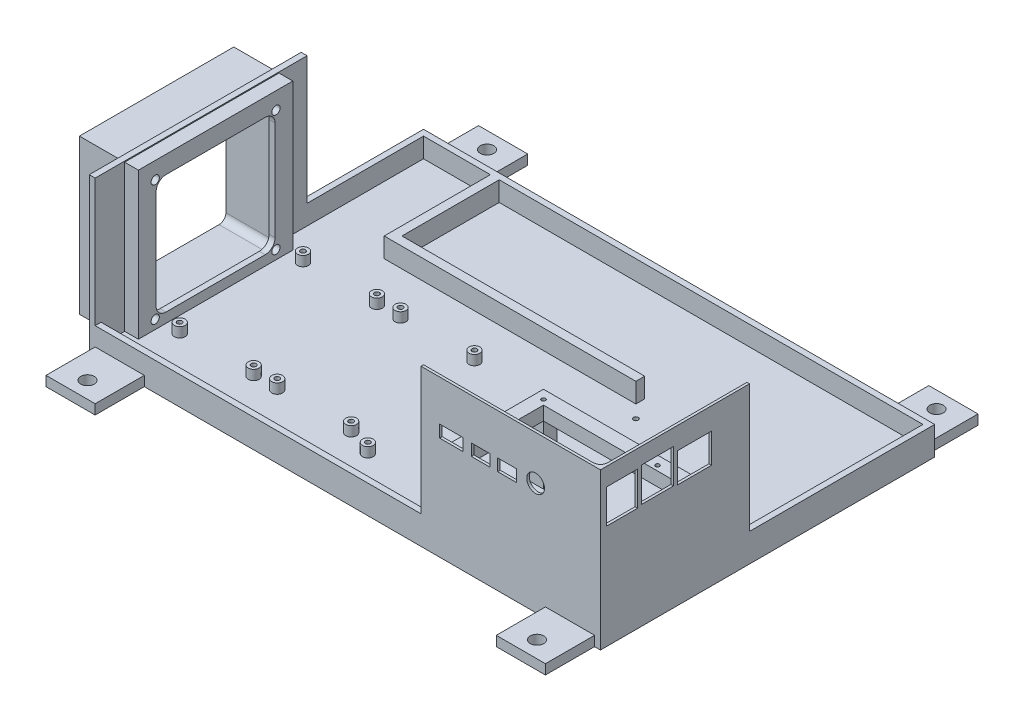
SolidWorks part; units mm, degrees
ref_plane "Front Plane" through (0, 0, 0) normal (0, 0, 1) x (1, 0, 0)
ref_plane "Top Plane" through (0, 0, 0) normal (0, 1, 0) x (1, 0, 0)
ref_plane "Right Plane" through (0, 0, 0) normal (1, 0, 0) x (0, 0, -1)
sketch "Sketch1" plane through (0, 0, 0) normal (0, 1, 0) x (1, 0, 0)
  line L1 (-130, -85) -> (130, -85)
  line L2 (-130, -85) -> (-130, 85)
  line L3 (-130, 85) -> (130, 85)
  line L4 (130, -85) -> (130, 85)
  line L5 (-130, -85) -> (130, 85) construction
  line L6 (-130, 85) -> (130, -85) construction
  point P0 (0, 0)
  dimension "D1" = 170
  dimension "D2" = 260
extrude "Floor" add sketch "Sketch1" along normal blind 4.3805
sketch "Sketch2" plane through (0, 4.3805, 0) normal (0, 1, 0) x (1, 0, 0)
  line L0 (127, -82) -> (127, 82)
  line L1 (127, 82) -> (-127, 82)
  line L2 (-127, 82) -> (-127, -82)
  line L3 (-127, -82) -> (127, -82)
  line L4 (130, -85) -> (130, 85)
  line L5 (130, 85) -> (-130, 85)
  line L6 (-130, 85) -> (-130, -85)
  line L7 (-130, -85) -> (130, -85)
  line L8 (130, -85) -> (130, 85)
  line L9 (130, 85) -> (-130, 85)
  line L10 (-130, 85) -> (-130, -85)
  line L11 (-130, -85) -> (130, -85)
  dimension "D1" = 0
  dimension "D2" = 3
extrude "Wall" add sketch "Sketch2" along normal blind 10
sketch "Sketch4" plane through (0, 4.3805, 0) normal (0, 1, 0) x (1, 0, 0)
  line L0 (120, -33) -> (49, -33)
  line L1 (127, -82) -> (42, -82)
  line L2 (127, -82) -> (127, -26)
  line L3 (127, -26) -> (42, -26)
  line L4 (42, -82) -> (42, -26)
  line L5 (49, -75) -> (49, -33)
  line L6 (120, -75) -> (49, -75)
  line L7 (120, -75) -> (120, -33)
  dimension "D1" = 85
  dimension "D2" = 56
  dimension "D3" = 7
extrude "Rpi stand" add sketch "Sketch4" along normal blind 7 from offset 30
sketch "Sketch7" plane through (0, 14.3805, 0) normal (0, 1, 0) x (1, 0, 0)
  line L0 (-127, 82) -> (-127, -82) construction
  line L1 (-130, -85) -> (-127, -85)
  line L2 (-130, -85) -> (-130, 22.7839)
  line L3 (-130, 22.7839) -> (-127, 22.7839)
  line L4 (-127, -85) -> (-127, 22.7839)
  line L5 (-127, -82) -> (127, -82) construction
  line L6 (130, -85) -> (38.7223, -85)
  line L7 (130, -85) -> (130, -52.9248)
  line L8 (127, -82) -> (38.7223, -82)
  line L9 (38.7223, -85) -> (38.7223, -82)
  line L10 (127, -82) -> (127, 82) construction
  line L12 (130, -52.9248) -> (130, -9.2525)
  line L13 (130, -9.2525) -> (127, -9.2525)
  line L14 (127, -82) -> (127, -9.2525)
  line L15 (-127, -82) -> (127, -82) construction
  line L16 (130, -85) -> (130, 85) construction
extrude "Temp support" add sketch "Sketch7" along normal blind 65
sketch "Sketch3" plane through (0, 0, 0) normal (0, 1, 0) x (1, 0, 0)
  line L0 (-114.3, 101.6) -> (114.3, 101.6) construction
  line L1 (-127, 85) -> (-102, 85)
  line L2 (-127, 85) -> (-127, 110)
  line L3 (-127, 110) -> (-102, 110)
  line L4 (-102, 85) -> (-102, 110)
  line L5 (127, 85) -> (102, 85)
  line L6 (127, 85) -> (127, 110)
  line L7 (127, 110) -> (102, 110)
  line L8 (102, 85) -> (102, 110)
  line L9 (-127, -85) -> (-102, -85)
  line L10 (-127, -85) -> (-127, -110)
  line L11 (-127, -110) -> (-102, -110)
  line L12 (-102, -85) -> (-102, -110)
  line L13 (127, -85) -> (102, -85)
  line L14 (127, -85) -> (127, -110)
  line L15 (127, -110) -> (102, -110)
  line L16 (102, -85) -> (102, -110)
  line L17 (114.3, 101.6) -> (114.3, -101.6) construction
  line L18 (114.3, -101.6) -> (-114.3, -101.6) construction
  line L19 (-114.3, -101.6) -> (-114.3, 101.6) construction
  line L20 (-130, 37.8738) -> (130, 37.8738) construction
  line L21 (130, 85) -> (-130, 85) construction
  line L22 (130, -9.2525) -> (130, 85) construction
  line L23 (0, 101.6) -> (0, -101.6) construction
  line L24 (-130, 22.7839) -> (-130, -85) construction
  line L29 (38.7223, -85) -> (130, -85) construction
  line L30 (-127, -85) -> (38.7223, -85) construction
  circle A0 centre (-114.3, 101.6) radius 3.429
  circle A1 centre (114.3, 101.6) radius 3.429
  circle A2 centre (114.3, -101.6) radius 3.429
  circle A3 centre (-114.3, -101.6) radius 3.429
  point P28 (-114.5, -85)
  point P29 (-102, -97.5)
  point P30 (114.5, -85)
  point P31 (-102, 97.5)
  dimension "D5" = 6.858
  dimension "D1" = 25
  dimension "D2" = 25
  dimension "D3" = 25
  dimension "D6" = 203.2
  dimension "D7" = 228.6
  dimension "D8" = 3
  dimension "D9" = 3
  dimension "D4" = 25
extrude "Brackets" add sketch "Sketch3" along normal blind 5
sketch "Sketch5" plane through (-130, 0, 0) normal (-1, 0, 0) x (0, 0, 1)
  line L0 (-8.5, 78.8805) -> (70, 78.8805)
  line L1 (-1, 4.3805) -> (62.5, 4.3805)
  line L2 (-4.5, 7.8805) -> (-4.5, 71.3805)
  line L3 (-1, 74.8805) -> (62.5, 74.8805)
  line L4 (66, 7.8805) -> (66, 71.3805)
  line L5 (70, 0.3805) -> (70, 78.8805)
  line L6 (-8.5, 0.3805) -> (70, 0.3805)
  line L7 (-8.5, 0.3805) -> (-8.5, 78.8805)
  line L8 (-4.5, 4.3805) -> (66, 4.3805) construction
  line L9 (110, 5) -> (110, 0) construction
  line L10 (-4.5, 4.3805) -> (-4.5, 74.8805) construction
  line L11 (-82, 4.3805) -> (82, 4.3805) construction
  line L12 (66, 4.3805) -> (66, 74.8805) construction
  line L13 (-4.5, 74.8805) -> (66, 74.8805) construction
  arc A0 (-1, 4.3805) -> (-4.5, 7.8805) centre (-1, 7.8805) cw
  arc A1 (62.5, 4.3805) -> (66, 7.8805) centre (62.5, 7.8805) ccw
  arc A2 (62.5, 74.8805) -> (66, 71.3805) centre (62.5, 71.3805) cw
  arc A3 (-4.5, 71.3805) -> (-1, 74.8805) centre (-1, 71.3805) cw
  dimension "D4" = 3.5
  dimension "D1" = 70.5
  dimension "D2" = 70.5
  dimension "D5" = 40
  dimension "D3" = 4
extrude "Fan Holder" add sketch "Sketch5" along normal blind 20 and the other way blind 10
sketch "Sketch8" plane through (-130, 0, 0) normal (-1, 0, 0) x (0, 0, 1)
  line L4 (-4.5, 71.3805) -> (-4.5, 7.8805)
  line L5 (-1, 4.3805) -> (62.5, 4.3805)
  line L6 (66, 7.8805) -> (66, 71.3805)
  line L7 (62.5, 74.8805) -> (-1, 74.8805)
  line L8 (-4.5, 71.3805) -> (-4.5, 7.8805)
  line L9 (-1, 4.3805) -> (62.5, 4.3805)
  line L10 (66, 7.8805) -> (66, 71.3805)
  line L20 (62.5, 74.8805) -> (-1, 74.8805)
  arc A2 (-4.5, 7.8805) -> (-1, 4.3805) centre (-1, 7.8805) ccw
  arc A3 (-4.5, 7.8805) -> (-1, 4.3805) centre (-1, 7.8805) ccw
  arc A4 (62.5, 4.3805) -> (66, 7.8805) centre (62.5, 7.8805) ccw
  arc A5 (62.5, 4.3805) -> (66, 7.8805) centre (62.5, 7.8805) ccw
  arc A8 (66, 71.3805) -> (62.5, 74.8805) centre (62.5, 71.3805) ccw
  arc A12 (66, 71.3805) -> (62.5, 74.8805) centre (62.5, 71.3805) ccw
  arc A14 (-1, 74.8805) -> (-4.5, 71.3805) centre (-1, 71.3805) ccw
  arc A15 (-1, 74.8805) -> (-4.5, 71.3805) centre (-1, 71.3805) ccw
  dimension "D1" = 0
extrude "Fan hole" cut sketch "Sketch8" against normal up to next (3 mm away)
sketch "Sketch11" plane through (-120, 0, 0) normal (-1, 0, 0) x (0, 0, 1)
  line L0 (-8.5, 39.6305) -> (70, 39.6305) construction
  line L1 (30.75, 78.8805) -> (30.75, 0.3805) construction
  line L3 (0.05, 8.9305) -> (61.45, 8.9305) construction
  line L4 (-8.5, 78.8805) -> (-8.5, 0.3805)
  line L5 (-8.5, 0.3805) -> (70, 0.3805)
  line L6 (70, 0.3805) -> (70, 78.8805)
  line L7 (70, 78.8805) -> (-8.5, 78.8805)
  line L8 (-8.5, 78.8805) -> (-8.5, 0.3805)
  line L9 (-8.5, 0.3805) -> (70, 0.3805)
  line L10 (70, 0.3805) -> (70, 78.8805)
  line L11 (70, 78.8805) -> (-8.5, 78.8805)
  line L12 (0.05, 8.9305) -> (0.05, 70.3305) construction
  line L13 (0.05, 70.3305) -> (61.45, 70.3305) construction
  line L14 (61.45, 8.9305) -> (61.45, 70.3305) construction
  line L15 (0.05, 8.9305) -> (61.45, 70.3305) construction
  line L16 (0.5, 69.8805) -> (0.5, 9.3805)
  line L17 (0.5, 9.3805) -> (61, 9.3805)
  line L18 (61, 9.3805) -> (61, 69.8805)
  line L19 (61, 69.8805) -> (0.5, 69.8805)
  line L20 (0.5, 64.8805) -> (0.5, 14.3805)
  line L21 (5.5, 9.3805) -> (56, 9.3805)
  line L22 (61, 14.3805) -> (61, 64.8805)
  line L23 (56, 69.8805) -> (5.5, 69.8805)
  line L24 (0.05, 70.3305) -> (61.45, 8.9305) construction
  arc A0 (0.5, 14.3805) -> (5.5, 9.3805) centre (5.5, 14.3805) ccw
  arc A1 (56, 9.3805) -> (61, 14.3805) centre (56, 14.3805) ccw
  arc A2 (61, 64.8805) -> (56, 69.8805) centre (56, 64.8805) ccw
  arc A3 (0.5, 64.8805) -> (5.5, 69.8805) centre (5.5, 64.8805) cw
  circle A4 centre (0.05, 70.3305) radius 2.1
  circle A5 centre (61.45, 70.3305) radius 2.1
  circle A6 centre (61.45, 8.9305) radius 2.1
  circle A7 centre (0.05, 8.9305) radius 2.1
  point P24 (30.75, 39.6305)
  point P34 (30.75, 39.6305)
  dimension "D3" = 5
  dimension "D6" = 4.2
  dimension "D4" = 61.4
  dimension "D5" = 61.4
  dimension "D1" = 0
  dimension "D2" = 9
extrude "Boss-Extrude9" add sketch "Sketch11" along normal blind 3
sketch "Sketch12" plane through (0, 34.3805, 0) normal (0, -1, 0) x (1, 0, 0)
  line L1 (42, 26) -> (49, 26)
  line L2 (42, 26) -> (42, 33)
  line L3 (42, 33) -> (49, 33)
  line L4 (49, 26) -> (49, 33)
  dimension "D1" = 7
  dimension "D2" = 7
extrude "Boss-Extrude10" add sketch "Sketch12" along normal up to next
sketch "Sketch13" plane through (0, 4.3805, 0) normal (0, 1, 0) x (1, 0, 0)
  line L0 (-127, -82) -> (127, -82) construction
  line L1 (-127, -85) -> (-127, 22.7839) construction
  line L2 (-112, -57) -> (-112, 5.7) construction
  line L3 (-112, 5.7) -> (-74.4, 5.7) construction
  line L4 (-112, -57) -> (-74.4, -57) construction
  line L5 (-74.4, 5.7) -> (-74.4, -57) construction
  line L6 (-74.4, 5.7) -> (-62.4, 5.7) construction
  line L7 (-62.4, 5.7) -> (-62.4, -57) construction
  line L8 (-62.4, -57) -> (-24.8, -57) construction
  line L9 (-24.8, -57) -> (-24.8, 5.7) construction
  line L10 (-24.8, 5.7) -> (-62.4, 5.7) construction
  line L11 (-74.4, -57) -> (-62.4, -57) construction
  line L12 (-24.8, -57) -> (62.83, -57) construction
  line L13 (62.83, -57) -> (62.83, -25.4) construction
  line L14 (62.83, -25.4) -> (105, -25.4) construction
  line L15 (105, -25.4) -> (105, -57) construction
  line L16 (105, -57) -> (62.83, -57) construction
  line L17 (118, 82) -> (118, 21.5) construction
  line L18 (-21.3, -57.85) -> (-21.3, 6.55) construction
  line L19 (127, 82) -> (-127, 82) construction
  line L20 (127, -9.2525) -> (127, 82) construction
  line L21 (118, 21.5) -> (120.7, 21.5) construction
  line L22 (118, 21.5) -> (41.5, 21.5) construction
  line L23 (-11.3, -62) -> (25.69, -62) construction
  line L24 (-11.3, -62) -> (-11.3, -21.4) construction
  line L25 (-11.3, -21.4) -> (25.69, -21.4) construction
  line L26 (25.69, -62) -> (25.69, -21.4) construction
  line L27 (-11.3, -62) -> (25.69, -21.4) construction
  line L28 (-11.3, -21.4) -> (25.69, -62) construction
  line L29 (130, -9.2525) -> (130, 85) construction
  line L30 (-127, -82) -> (38.7223, -82) construction
  circle A0 centre (-112, -57) radius 1.25
  circle A1 centre (-112, 5.7) radius 1.25
  circle A2 centre (-74.4, 5.7) radius 1.25
  circle A3 centre (-74.4, -57) radius 1.25
  circle A4 centre (-62.4, 5.7) radius 1.25
  circle A5 centre (-62.4, -57) radius 1.25
  circle A6 centre (-24.8, -57) radius 1.25
  circle A7 centre (-24.8, 5.7) radius 1.25
  circle A12 centre (120.7, 21.5) radius 1.25
  circle A13 centre (41.5, 21.5) radius 1.25
  circle A14 centre (-112, 5.7) radius 2.75
  circle A15 centre (-112, -57) radius 2.75
  circle A16 centre (-74.4, 5.7) radius 2.75
  circle A17 centre (-62.4, 5.7) radius 2.75
  circle A18 centre (-74.4, -57) radius 2.75
  circle A19 centre (-62.4, -57) radius 2.75
  circle A20 centre (-24.8, -57) radius 2.75
  circle A21 centre (-24.8, 5.7) radius 2.75
  circle A22 centre (62.83, -57) radius 2.5
  circle A23 centre (62.83, -25.4) radius 2.5
  circle A24 centre (105, -25.4) radius 2.5
  circle A25 centre (105, -57) radius 2.5
  circle A26 centre (-11.3, -62) radius 1.25
  circle A28 centre (-11.3, -62) radius 2.75
  circle A30 centre (-74.4, 5.7) radius 1.65 construction
  circle A31 centre (104.2333, -41.2) radius 1.5 construction
  circle A32 centre (104.2333, -41.2) radius 1.5 construction
  circle A33 centre (63.5933, -41.2) radius 1.5 construction
  circle A34 centre (63.5933, -41.2) radius 1.5 construction
  circle A35 centre (104.2333, -41.2) radius 3
  circle A36 centre (63.5933, -41.2) radius 3
  circle A37 centre (-11.3, -21.4) radius 1.25
  circle A38 centre (25.69, -21.4) radius 1.25
  circle A39 centre (25.69, -62) radius 1.25
  circle A40 centre (-11.3, -21.4) radius 2.75
  circle A41 centre (25.69, -21.4) radius 2.75
  circle A42 centre (25.69, -62) radius 2.75
  circle A43 centre (25.69, -21.4) radius 1.5 construction
  circle A44 centre (25.69, -21.4) radius 1.5 construction
  point P6 (-127, -31.108)
  point P8 (7.195, -41.7)
  dimension "D1" = 25
  dimension "D2" = 15
  dimension "D3" = 2.5
  dimension "D6" = 1.5
  dimension "D7" = 2.5
  dimension "D8" = 10
  dimension "D11" = 20
  dimension "D25" = 2.5
  dimension "D27" = 2.5
  dimension "D4" = 5
  dimension "D5" = 25
  dimension "D9" = 12
  dimension "D10" = 1.5
  dimension "D17" = 31.6
  dimension "D19" = 42.17
  dimension "D22" = 60.5
  dimension "D23" = 9
  dimension "D24" = 2.7
  dimension "D26" = 76.5
  dimension "D28" = 1.5
extrude "Built in Standoffs" add sketch "Sketch13" along normal blind 5 contours A1 | A16 A2 | A2 | A17 A4 | A4 | A14 A1 | A21 A7 | A7 | A15 A0 | A0 | A18 A3 | A3 | A19 A5 | A5 | A20 A6 | A6 | A22 | A23 | A24 A32 | A32 | A25 | A36 | A35 | A28 A26 | A26 | A40 A37 | A37 | A41 A38 | A38 | A42 A39 | A39 region at (-112, 4.3805, 57) region at (-112, 4.3805, -5.7) region at (-74.4, 4.3805, -5.7) region at (-74.4, 4.3805, 57) region at (-62.4, 4.3805, -5.7) region at (-62.4, 4.3805, 57) region at (-24.8, 4.3805, 57) region at (-24.8, 4.3805, -5.7) region at (-114.6722, 4.3805, -5.7) region at (-114.6722, 4.3805, 57) region at (-77.0722, 4.3805, -5.7) region at (-65.0722, 4.3805, -5.7) region at (-77.0722, 4.3805, 57) region at (-65.0722, 4.3805, 57) region at (-27.4722, 4.3805, 57) region at (-27.4722, 4.3805, -5.7) region at (62.83, 4.3805, 57) region at (62.83, 4.3805, 25.4) region at (105, 4.3805, 25.4) region at (105, 4.3805, 57) region at (-11.3, 4.3805, 62) region at (-13.9722, 4.3805, 62) region at (104.2333, 4.3805, 41.2) region at (63.5933, 4.3805, 41.2) region at (-11.3, 4.3805, 21.4) region at (25.69, 4.3805, 21.4) region at (25.69, 4.3805, 62) region at (-13.9722, 4.3805, 21.4) region at (23.0178, 4.3805, 21.4) region at (23.0178, 4.3805, 62)
sketch "Sketch19" plane through (0, 9.3805, 0) normal (0, 1, 0) x (1, 0, 0)
  circle A0 centre (104.2333, -41.2) radius 1.25
  circle A1 centre (63.5933, -41.2) radius 1.25
  dimension "D1" = 2.5
  dimension "D2" = 2.5
extrude "Bread board holes" cut sketch "Sketch19" against normal blind 7
sketch "Sketch14" plane through (0, 4.3805, 0) normal (0, 1, 0) x (1, 0, 0)
  line L0 (127, 82) -> (-88, 82)
  line L1 (127, 82) -> (-127, 82) construction
  line L2 (-88, 82) -> (-88, 32)
  line L3 (-88, 32) -> (127, 32)
  line L4 (127, -82) -> (127, 82) construction
  line L5 (127, 32) -> (127, 82)
  dimension "D1" = 215
  dimension "D2" = 50
extrude "Screw Holes" cut sketch "Sketch13<4>" against normal blind 7 from surface contours A37 | A38 | A26 | A39 | A1 | A0 | A3 | A5 | A2 | A4 | A7 | A6 | A32 region at (-11.3, 4.3805, 62) region at (-11.3, 4.3805, 21.4) region at (25.69, 4.3805, 21.4) region at (25.69, 4.3805, 62) starting at face at (-112, 9.3805, -2.95)
sketch "Sketch13<4>" plane through (0, 4.3805, 0) normal (0, 1, 0) x (1, 0, 0) same geometry as "Sketch13"
extrude "Driver Screw Holes" cut sketch "Sketch13<5>" against normal blind 3 contours A13 | A12
sketch "Sketch13<5>" plane through (0, 4.3805, 0) normal (0, 1, 0) x (1, 0, 0) same geometry as "Sketch13"
sketch "Sketch16" plane through (0, 4.3805, 0) normal (0, 1, 0) x (1, 0, 0)
  line L0 (-93, 82) -> (-93, 28)
  line L1 (-93, 28) -> (35, 28)
  line L2 (-88.5, 82) -> (-88.5, 32.5)
  line L3 (-88.5, 32.5) -> (35, 32.5)
  line L10 (-88, 82) -> (-88, 33) construction
  line L11 (-88, 33) -> (29.1074, 33) construction
  line L14 (-93, 28) -> (127, 28) construction
  line L16 (-88, 33) -> (127, 33) construction
  line L17 (-88.5, 82) -> (-93, 82)
  line L20 (35, 28) -> (35, 32.5)
  line L21 (-88.5, 32.5) -> (29.1074, 32.5) construction
  line L25 (-88, 33) -> (127, 33)
  line L26 (127, 33) -> (127, 82)
  line L27 (127, 82) -> (-88, 82)
  line L28 (-88, 82) -> (-88, 33)
  line L29 (-88, 33) -> (127, 33) construction
  line L30 (127, 33) -> (127, 82) construction
  line L31 (127, 82) -> (-88, 82) construction
  line L32 (-88, 82) -> (-88, 33) construction
  line L57 (-88, 82) -> (-88, 33) construction
  line L58 (127, 82) -> (-127, 82) construction
  dimension "D3" = 0.5
  dimension "D5" = 128
  dimension "D1" = 0
  dimension "D2" = 5
extrude "Power supply wall" add sketch "Sketch16" along normal blind 10 contours L2 L3 L20 L1 L0 L17
sketch "Sketch17" plane through (0, 41.3805, 0) normal (0, 1, 0) x (1, 0, 0)
  circle A0 centre (46.5, -30.5) radius 1.025
  circle A1 centre (104.5, -30.5) radius 1.025
  circle A2 centre (104.5, -79.5) radius 1.025
  circle A3 centre (46.5, -79.5) radius 1.025
  dimension "D1" = 2.05
extrude "Cut-Extrude3" cut sketch "Sketch17" against normal blind 6
sketch "Sketch20" plane through (0, 0, 85) normal (0, 0, 1) x (1, 0, 0)
  line L1 (49.6827, 57.1504) -> (58.6882, 57.1504) construction
  line L2 (49.6827, 57.1504) -> (49.6827, 53.9554) construction
  line L3 (49.6827, 53.9554) -> (58.6882, 53.9554) construction
  line L4 (58.6882, 57.1504) -> (58.6882, 53.9554) construction
  line L5 (79.2167, 56.9908) -> (85.8798, 56.9908) construction
  line L6 (79.2167, 56.9908) -> (79.2167, 53.9258) construction
  line L7 (79.2167, 53.9258) -> (85.8798, 53.9258) construction
  line L8 (85.8798, 56.9908) -> (85.8798, 53.9258) construction
  line L9 (65.7798, 56.9112) -> (72.2962, 56.9112) construction
  line L10 (65.7798, 56.9112) -> (65.7798, 53.9475) construction
  line L11 (65.7798, 53.9475) -> (72.2962, 53.9475) construction
  line L12 (72.2962, 56.9112) -> (72.2962, 53.9475) construction
  line L13 (48.1827, 58.6504) -> (60.1882, 58.6504)
  line L14 (60.1882, 58.6504) -> (60.1882, 52.4554)
  line L15 (48.1827, 52.4554) -> (60.1882, 52.4554)
  line L16 (48.1827, 58.6504) -> (48.1827, 52.4554)
  line L17 (77.7167, 58.4908) -> (87.3798, 58.4908)
  line L18 (87.3798, 58.4908) -> (87.3798, 52.4258)
  line L19 (77.7167, 52.4258) -> (87.3798, 52.4258)
  line L20 (77.7167, 58.4908) -> (77.7167, 52.4258)
  line L21 (64.2798, 58.4112) -> (73.7962, 58.4112)
  line L22 (73.7962, 58.4112) -> (73.7962, 52.4475)
  line L23 (64.2798, 52.4475) -> (73.7962, 52.4475)
  line L24 (64.2798, 58.4112) -> (64.2798, 52.4475)
  circle A0 centre (97, 56.9705) radius 4.5
  dimension "D1" = 9
  dimension "D2" = 1.5
extrude "Cut-Extrude5" cut sketch "Sketch20" against normal up to next
sketch "Sketch21" plane through (0, 79.3805, 0) normal (0, 1, 0) x (1, 0, 0)
  line L0 (125, -26.3) -> (46, -26.3) construction
  line L1 (42.3, -30) -> (42.3, -80) construction
  line L2 (46, -83.7) -> (125, -83.7)
  line L3 (128.7, -80) -> (128.7, -30)
  line L4 (128, -80) -> (128, -30)
  line L5 (125, -27) -> (46, -27)
  line L6 (43, -30) -> (43, -80)
  line L7 (46, -83) -> (125, -83)
  line L8 (128, -80) -> (128, -30) construction
  line L9 (125, -27) -> (46, -27) construction
  line L10 (43, -30) -> (43, -80) construction
  line L11 (46, -83) -> (125, -83) construction
  line L28 (46, -83.7) -> (37.0142, -83.7)
  line L29 (37.0142, -83.7) -> (37.0142, -5.7053)
  line L30 (37.0142, -5.7053) -> (128.7, -5.7053)
  line L31 (128.7, -5.7053) -> (128.7, -30)
  arc A0 (46, -26.3) -> (42.3, -30) centre (46, -30) ccw construction
  arc A1 (42.3, -80) -> (46, -83.7) centre (46, -80) ccw construction
  arc A2 (125, -83.7) -> (128.7, -80) centre (125, -80) ccw
  arc A3 (128.7, -30) -> (125, -26.3) centre (125, -30) ccw construction
  arc A4 (128, -30) -> (125, -27) centre (125, -30) ccw
  arc A5 (46, -27) -> (43, -30) centre (46, -30) ccw
  arc A6 (43, -80) -> (46, -83) centre (46, -80) ccw
  arc A7 (125, -83) -> (128, -80) centre (125, -80) ccw
  arc A8 (128, -30) -> (125, -27) centre (125, -30) ccw construction
  arc A9 (46, -27) -> (43, -30) centre (46, -30) ccw construction
  arc A10 (43, -80) -> (46, -83) centre (46, -80) ccw construction
  arc A11 (125, -83) -> (128, -80) centre (125, -80) ccw construction
  dimension "D1" = 0
  dimension "D2" = 0.7
extrude "Cut-Extrude6" cut sketch "Sketch21" against normal blind 35 contours L2 A2 L3 L31 L30 L29 L28
sketch "Sketch22" plane through (130, 0, 0) normal (1, 0, 0) x (0, 0, -1)
  line L0 (-81.966, 70.2905) -> (-66.1499, 70.2905)
  line L1 (-81.166, 69.4905) -> (-66.9499, 69.4905) construction
  line L2 (-81.166, 69.4905) -> (-81.166, 53.8427) construction
  line L3 (-81.166, 53.8427) -> (-66.9499, 53.8427) construction
  line L4 (-66.9499, 69.4905) -> (-66.9499, 53.8427) construction
  line L5 (-63.3011, 70.2905) -> (-48.6526, 70.2905) construction
  line L6 (-63.3011, 70.2905) -> (-63.3011, 54.5222) construction
  line L7 (-63.3011, 54.5222) -> (-48.6526, 54.5222) construction
  line L8 (-48.6526, 70.2905) -> (-48.6526, 54.5222) construction
  line L9 (-45.1414, 67.4119) -> (-29.3586, 67.4119) construction
  line L10 (-45.1414, 67.4119) -> (-45.1414, 53.9605) construction
  line L11 (-45.1414, 53.9605) -> (-29.3586, 53.9605) construction
  line L12 (-29.3586, 67.4119) -> (-29.3586, 53.9605) construction
  line L13 (-66.1499, 70.2905) -> (-66.1499, 53.0427)
  line L14 (-81.966, 53.0427) -> (-66.1499, 53.0427)
  line L15 (-81.966, 70.2905) -> (-81.966, 53.0427)
  line L16 (-64.1011, 71.0905) -> (-47.8526, 71.0905)
  line L17 (-47.8526, 71.0905) -> (-47.8526, 53.7222)
  line L18 (-64.1011, 53.7222) -> (-47.8526, 53.7222)
  line L19 (-64.1011, 71.0905) -> (-64.1011, 53.7222)
  line L20 (-45.9414, 68.2119) -> (-28.5586, 68.2119)
  line L21 (-28.5586, 68.2119) -> (-28.5586, 53.1605)
  line L22 (-45.9414, 53.1605) -> (-28.5586, 53.1605)
  line L23 (-45.9414, 68.2119) -> (-45.9414, 53.1605)
  line L24 (-70.9672, 69.4905) -> (-73.95, 69.4905) construction
  line L25 (-85, 79.3805) -> (-85, 0) construction
  line L26 (-85, 0) -> (85, 0) construction
  arc A0 (-29.3, 67.2705) -> (-29.5, 67.4705) centre (-29.5, 67.2705) ccw construction
  point P12 (-73.0445, 69.4905)
  point P15 (-81.966, 70.2905)
  point P16 (-67.1155, 69.4905)
  point P17 (-67.1, 53.8705)
  point P18 (0, 0)
  point P21 (-81.166, 69.4905)
  point P22 (-63.3011, 70.2905)
  dimension "D2" = 3.834
  dimension "D3" = 14.2161
  dimension "D4" = 15.6478
  dimension "D5" = 3.6488
  dimension "D6" = 14.6485
  dimension "D7" = 15.7683
  dimension "D8" = 70.2905
  dimension "D9" = 13.4514
  dimension "D1" = 0.8
extrude "Cut-Extrude7" cut sketch "Sketch22" against normal up to next
equation "\"D2@Sketch3\"=\"D1@Sketch3\""
